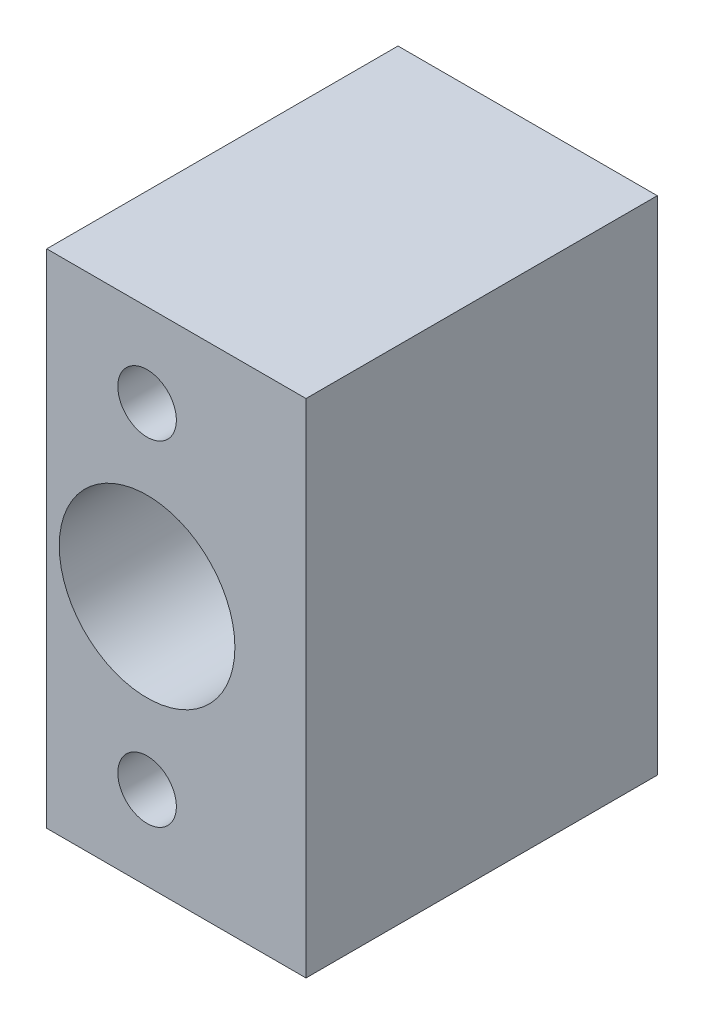
SolidWorks part; units mm, degrees
material "6061-T4 (SS)"
ref_plane "Front Plane" through (0, 0, 0) normal (0, 0, 1) x (1, 0, 0)
ref_plane "Top Plane" through (0, 0, 0) normal (0, 1, 0) x (1, 0, 0)
ref_plane "Right Plane" through (0, 0, 0) normal (1, 0, 0) x (0, 0, -1)
sketch "Sketch1" plane through (0, 0, 0) normal (0, 0, 1) x (1, 0, 0)
  line L5 (-6, 6) -> (0, 0) construction
  line L6 (0, 0) -> (6, 6) construction
  line L7 (9.5, 15) -> (-9.5, 15)
  line L8 (9.5, 15) -> (9.5, -15)
  line L9 (9.5, -15) -> (-9.5, -15)
  line L10 (-9.5, 15) -> (-9.5, -15)
  line L11 (9.5, 15) -> (-9.5, -15) construction
  line L12 (9.5, -15) -> (-9.5, 15) construction
  point P0 (0, 0)
  dimension "D1" = 19
  dimension "D4" = 30
extrude "Boss-Extrude1" add sketch "Sketch1" along normal blind 18
sketch "Sketch2" plane through (0, 0, 18) normal (0, 0, 1) x (1, 0, 0)
  circle A0 centre (0, 0) radius 5.25
  dimension "D1" = 10.5
extrude "Cut-Extrude1" cut sketch "Sketch2" against normal blind 11.5 contours A0
sketch "Sketch4" plane through (0, 0, 6.5) normal (0, 0, 1) x (1, 0, 0)
  circle A0 centre (0, 0) radius 4.8
  dimension "D1" = 9.6
extrude "Cut-Extrude3" cut sketch "Sketch4" against normal blind 1
sketch "Sketch5" plane through (0, 0, 5.5) normal (0, 0, 1) x (1, 0, 0)
  circle A0 centre (0, 0) radius 2.36
  dimension "D1" = 4.72
extrude "Cut-Extrude4" cut sketch "Sketch5" against normal blind 5 and the other way through all
sketch "Sketch6" plane through (0, 0, 0) normal (0, 0, 1) x (1, 0, 0)
  line L0 (-6, 15) -> (-6, -15)
  line L3 (9.5, 15) -> (-9.5, 15) construction
  line L4 (-9.5, -15) -> (9.5, -15) construction
  circle A0 centre (0, 0) radius 5.25 construction
  point P6 (-6, 0)
  dimension "D1" = 6
extrude "Cut-Extrude6" cut sketch "Sketch6" against normal through all and the other way through all flip side to cut
sketch "Sketch11" plane through (0, 0, 0) normal (0, 0, -1) x (-1, 0, 0)
  line L1 (6, 15) -> (-9.5, 15)
  line L2 (6, 15) -> (6, -15)
  line L3 (6, -15) -> (-9.5, -15)
  line L4 (-9.5, 15) -> (-9.5, -15)
extrude "Boss-Extrude5" add sketch "Sketch11" along normal blind 5
sketch "Sketch12" plane through (0, 0, -5) normal (0, 0, -1) x (-1, 0, 0)
  circle A0 centre (0, 0) radius 4
  dimension "D1" = 8
extrude "Cut-Extrude8" cut sketch "Sketch12" against normal blind 5
sketch "Sketch13" plane through (0, 0, -5) normal (0, 0, -1) x (-1, 0, 0)
  line L2 (6, 15) -> (-9.5, 15) construction
  line L3 (0, 15) -> (0, -15) construction
  line L4 (-9.5, -15) -> (6, -15) construction
  circle A1 centre (0, -10) radius 1.75
  circle A2 centre (0, 10) radius 1.75
  point P0 (0, 5)
  point P4 (0, -5)
  point P6 (0, 0)
  dimension "D3" = 3.5
  dimension "D4" = 10
  dimension "D1" = 5
  dimension "D2" = 5
extrude "Cut-Extrude9" cut sketch "Sketch13" against normal through all
sketch "Sketch14" plane through (0, 0, 5.5) normal (0, 0, 1) x (1, 0, 0)
  circle A0 centre (0, 0) radius 3
  dimension "D1" = 6
extrude "Cut-Extrude10" cut sketch "Sketch14" against normal blind 1
sketch "Sketch15" plane through (0, -15, 0) normal (0, -1, 0) x (1, 0, 0)
  line L1 (-6, -5) -> (9.5, -5) construction
  line L2 (-6, -5) -> (-6, 16) construction
  line L3 (-6, 16) -> (9.5, 16)
  line L4 (9.5, -5) -> (9.5, 16) construction
  line L5 (9.5, 18) -> (9.5, -5) construction
  line L6 (-6, 16) -> (9.5, 16)
  line L7 (-6, 16) -> (-6, 17) construction
  line L8 (-6, 17) -> (9.5, 17) construction
  line L9 (9.5, 16) -> (9.5, 17) construction
  line L11 (-6, 18) -> (9.5, 18)
  line L12 (-6, 18) -> (-6, 16)
  line L13 (-6, 16) -> (9.5, 16)
  line L14 (9.5, 18) -> (9.5, 16)
  line M5 (9.5, 18) -> (-6, 18)
  line M6 (-6, 18) -> (-6, -5)
  line M8 (9.5, -5) -> (9.5, 18)
  dimension "D1" = 21
  dimension "D2" = 1
extrude "Cut-Extrude11" cut sketch "Sketch15" against normal blind 41 contours L3 M6 M8 M5 region at (1.75, -15, 17)
ref_axis "Axis1" through (-3.468, -10.0994, -1.5696) along (0.3898, 0.7544, 0.5281)
ref_plane "Plane2" through (-6, -15, -5) normal (0.3898, 0.7544, 0.5281) x (0.9209, -0.3193, -0.2235)
sketch "Sketch17" plane through (-6, -15, -5) normal (0.3898, 0.7544, 0.5281) x (0.9209, -0.3193, -0.2235)
  circle A0 centre (0, 0) radius 5
  dimension "D1" = 10
extrude "Cut-Extrude12" cut sketch "Sketch17" along normal blind 2
sketch "Sketch18" plane through (-5.5724, -10.7852, -7.5496) normal (-0.3898, -0.7544, -0.5281) x (0.9209, -0.3193, -0.2235)
  point P0 (0.3822, 4.5058)
sketch "Sketch20" plane through (0, 0, -5) normal (0, 0, -1) x (-1, 0, 0)
  circle A0 centre (0, 10) radius 3.81
  circle A1 centre (0, -10) radius 3.81
  circle A2 centre (0, -10) radius 1.75 construction
  dimension "D1" = 7.62
extrude "Cut-Extrude13" cut sketch "Sketch20" against normal blind 9
